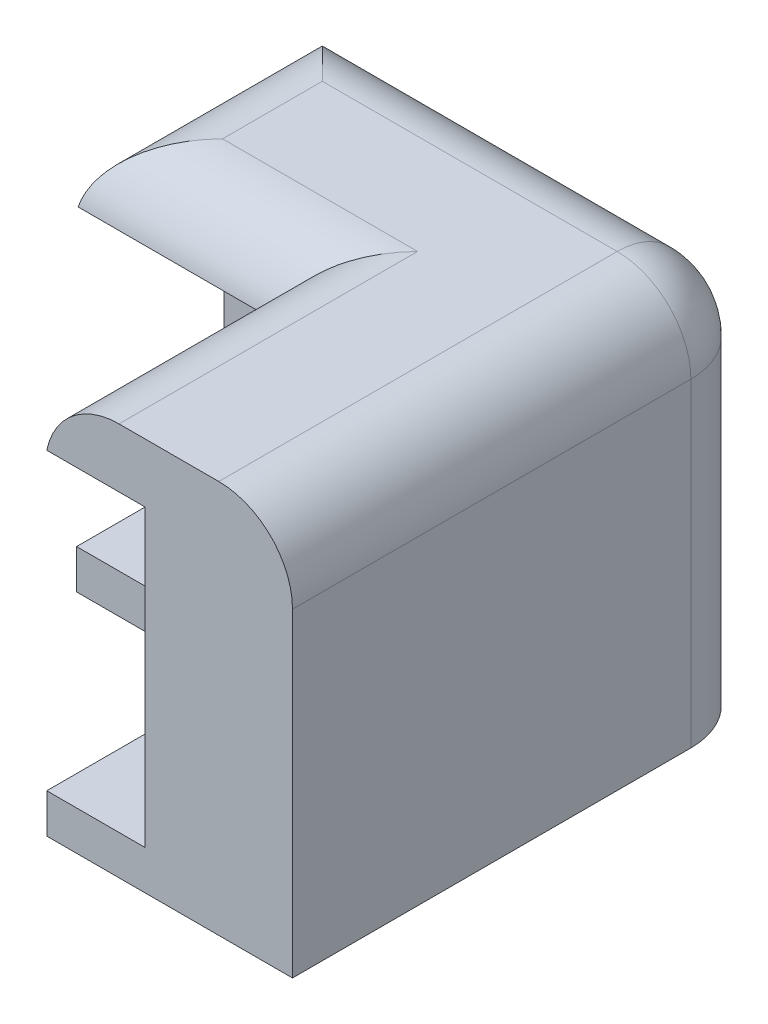
SolidWorks part; units mm, degrees
ref_plane "Спереди" through (0, 0, 0) normal (0, 0, 1) x (1, 0, 0)
ref_plane "Сверху" through (0, 0, 0) normal (0, 1, 0) x (1, 0, 0)
ref_plane "Справа" through (0, 0, 0) normal (1, 0, 0) x (0, 0, -1)
other "Configuration Table"
sketch "Основа" plane through (0, 0, 0) normal (0, 1, 0) x (1, 0, 0)
  line L1 (-109, -67) -> (109, -67)
  line L2 (-109, -67) -> (-109, 67)
  line L3 (-109, 67) -> (109, 67)
  line L4 (109, -67) -> (109, 67)
  line L5 (-109, -67) -> (109, 67) construction
  line L6 (-109, 67) -> (109, -67) construction
  line L7 (-99, -57) -> (99, -57)
  line L8 (-99, -57) -> (-99, 57)
  line L9 (-99, 57) -> (99, 57)
  line L10 (99, -57) -> (99, 57)
  line L11 (0, 57) -> (0, -57) construction
  line L12 (-99, 0) -> (99, 0) construction
  point P0 (0, 0)
  point P6 (0, 0)
  dimension "D1" = 134
  dimension "D2" = 218
  dimension "D3" = 114
  dimension "D4" = 198
extrude "Бобышка-Вытянуть2" add sketch "Основа" along normal blind 16
sketch "Эскиз2" plane through (-109, 0, 0) normal (-1, 0, 0) x (0, 0, 1)
  line L0 (0, 0) -> (0, 17.044) construction
  line L1 (63, 1.6) -> (-63, 1.6)
  line L2 (-63, 1.6) -> (-63, 13.6)
  line L3 (-63, 13.6) -> (63, 13.6)
  line L4 (-67, 0) -> (67, 0) construction
  line L5 (63, 1.6) -> (63, 13.6)
  point P10 (0, 13.6)
  point P11 (0, 1.6)
  dimension "D1" = 63
  dimension "D2" = 1.6
  dimension "D3" = 12
extrude "Вырез-Вытянуть1" cut sketch "Эскиз2" against normal blind 212
sketch "Эскиз3" plane through (0, 0, 67) normal (0, 0, 1) x (1, 0, 0)
  line L0 (0, 0) -> (0, 16) construction
  line L1 (-109, 16) -> (109, 16) construction
  line L2 (-109, 16) -> (-109, 0) construction
  line L3 (-91, 16) -> (91, 16)
  line L4 (-91, 16) -> (-91, 1.6)
  line L5 (-91, 1.6) -> (91, 1.6)
  line L6 (91, 16) -> (91, 1.6)
  line L7 (109, 16) -> (109, 0) construction
  line L8 (-109, 0) -> (109, 0) construction
  dimension "D1" = 18
  dimension "D2" = 18
  dimension "D3" = 1.6
extrude "Вырез-Вытянуть2" cut sketch "Эскиз3" against normal blind 134
sketch "Эскиз4" plane through (0, 1.6, 0) normal (0, 1, 0) x (1, 0, 0)
  line L0 (-91, 62) -> (91, 62) construction
  line L1 (-91, 67) -> (-91, 57) construction
  line L2 (91, 67) -> (91, 57) construction
  line L3 (-91, -62) -> (91, -62) construction
  line L4 (-91, -57) -> (-91, -67) construction
  line L5 (91, -57) -> (91, -67) construction
  line L6 (0, 67) -> (0, -65.4181) construction
  line L7 (-91, 67) -> (91, 67) construction
  line L8 (-74.6989, 67) -> (-74.6989, -67) construction
  line L9 (-91, -67) -> (91, -67) construction
  circle A0 centre (-74.6989, 62) radius 1
  circle A1 centre (-74.6989, -62) radius 1
  circle A2 centre (74.6989, -62) radius 1
  circle A3 centre (74.6989, 62) radius 1
extrude "Вырез-Вытянуть3" cut sketch "Эскиз4" against normal blind 1.6
fillet "Скругление1" radius 3 4 edges at (-109, 8, -67) (109, 8, -67) (109, 8, 67) (-109, 8, 67)
fillet "Скругление2" radius 3 10 edges at (-91, 16, -62) (-95, 16, -57) (-99, 16, 0) (-95, 16, 57) (-91, 16, 62) (-98.5, 16, 67) (-108.1213, 16, 66.1213) (-109, 16, 0) (-108.1213, 16, -66.1213) (-98.5, 16, -67)
fillet "Скругление3" radius 3 10 edges at (108.1213, 16, 66.1213) (98.5, 16, 67) (91, 16, 62) (95, 16, 57) (99, 16, 0) (95, 16, -57) (91, 16, -62) (98.5, 16, -67) (108.1213, 16, -66.1213) (109, 16, 0)
sketch "Эскиз5" plane through (0, 1.6, 0) normal (0, 1, 0) x (1, 0, 0)
  line L1 (91, 67) -> (-121.7819, 67)
  line L2 (91, 67) -> (91, -76.9625)
  line L3 (91, -76.9625) -> (-121.7819, -76.9625)
  line L4 (-121.7819, 67) -> (-121.7819, -76.9625)
sketch "Эскиз6" plane through (0, 0, -67) normal (0, 0, -1) x (-1, 0, 0)
  line L0 (-106, 0) -> (106, 0) construction
  line L1 (-91, 0) -> (115.898, 0)
  line L2 (-91, 0) -> (-91, 19.1774)
  line L3 (-91, 19.1774) -> (115.898, 19.1774)
  line L4 (115.898, 0) -> (115.898, 19.1774)
extrude "Вырез-Вытянуть5" cut sketch "Эскиз6" against normal blind 200
sketch "Эскиз7" plane through (109, 0, 0) normal (1, 0, 0) x (0, 0, -1)
  line L0 (-64, 0) -> (64, 0) construction
  line L1 (47.7864, 0) -> (-75.2385, 0)
  line L2 (47.7864, 0) -> (47.7864, 17.5669)
  line L3 (47.7864, 17.5669) -> (-75.2385, 17.5669)
  line L4 (-75.2385, 0) -> (-75.2385, 17.5669)
extrude "Вырез-Вытянуть6" cut sketch "Эскиз7" against normal blind 300
